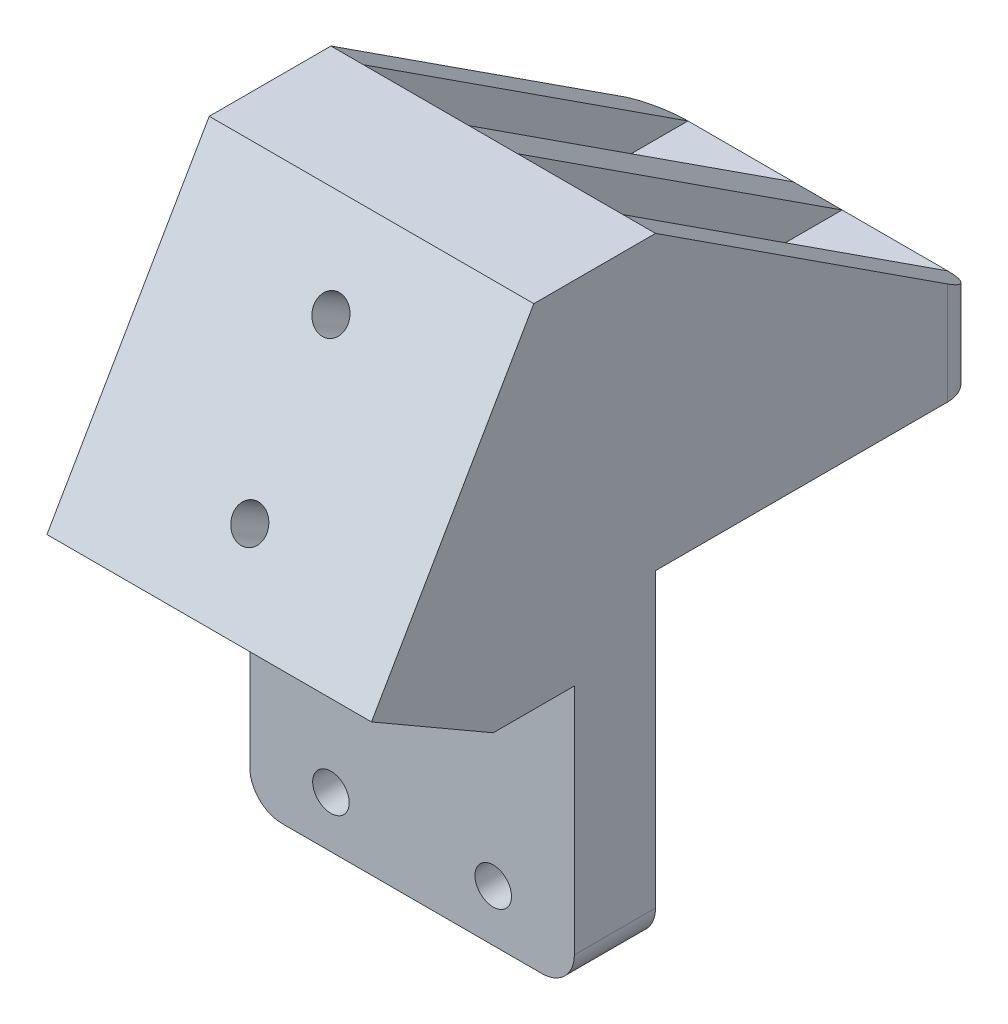
SolidWorks part; units mm, degrees
ref_plane "Plan de face" through (0, 0, 0) normal (0, 0, 1) x (1, 0, 0)
ref_plane "Plan de dessus" through (0, 0, 0) normal (0, 1, 0) x (1, 0, 0)
ref_plane "Plan de droite" through (0, 0, 0) normal (1, 0, 0) x (0, 0, -1)
sketch "Esquisse1" plane through (0, 0, 0) normal (1, 0, 0) x (0, 0, -1)
  line L0 (0, 0) -> (40, 0)
  line L1 (40, 0) -> (40, 10)
  line L2 (40, 10) -> (0, 10)
  line L3 (0, 10) -> (0, 36)
  line L4 (0, 36) -> (-15, 36)
  line L5 (-15, 36) -> (-35, 1.359)
  line L6 (-35, 1.359) -> (-20, -7.3013)
  line L7 (-20, -7.3013) -> (-10, -7.3013)
  line L8 (-10, -7.3013) -> (-10, -40)
  line L9 (-10, -40) -> (0, -40)
  line L10 (0, -40) -> (0, 0)
  point P3 (0, 37.6022)
  point P13 (-19.0235, -4.9783)
  dimension "D1" = 10
  dimension "D2" = 10
  dimension "D3" = 26
  dimension "D4" = 15
  dimension "D5" = 30
  dimension "D6" = 40
  dimension "D7" = 40
  dimension "D8" = 40
  dimension "D9" = 90
  dimension "D10" = 10
extrude "Boss.-Extru.1" add sketch "Esquisse1" along normal blind 40
sketch "Esquisse2" plane through (0, 10, 0) normal (0, 1, 0) x (1, 0, 0)
  line L0 (0, 20) -> (40, 20) construction
  line L1 (0, 40) -> (0, 0) construction
  line L2 (40, 40) -> (40, 0) construction
  line L3 (20, 20) -> (20, 40) construction
  line L4 (40, 40) -> (0, 40) construction
  circle A0 centre (10, 30) radius 2.25
  circle A1 centre (30, 30) radius 2.25
  circle A2 centre (30, 10) radius 2.25
  circle A3 centre (10, 10) radius 2.25
  dimension "D1" = 4.5
  dimension "D2" = 20
  dimension "D3" = 20
extrude "Enlèv. mat.-Extru.1" cut sketch "Esquisse2" against normal through all both and the other way through all
sketch "Esquisse3" plane through (0, 0, 10) normal (0, 0, 1) x (1, 0, 0)
  line L0 (20, -40) -> (20, -23.6506) construction
  line L1 (40, -40) -> (0, -40) construction
  line L2 (20, -23.6506) -> (0, -23.6506) construction
  line L3 (0, -7.3013) -> (0, -40) construction
  circle A0 centre (10, -33.6506) radius 2.25
  circle A1 centre (30, -33.6506) radius 2.25
  circle A2 centre (30, -13.6506) radius 2.25
  circle A3 centre (10, -13.6506) radius 2.25
  dimension "D1" = 20
  dimension "D2" = 20
  dimension "D3" = 4.5
extrude "Enlèv. mat.-Extru.2" cut sketch "Esquisse3" against normal through all both and the other way through all
sketch "Esquisse4" plane through (0, 15.4952, 26.8385) normal (0, 0.5, 0.866) x (1, 0, 0)
  line L0 (20, -16.3231) -> (20, 23.6769) construction
  line L1 (40, -16.3231) -> (0, -16.3231) construction
  line L2 (40, 23.6769) -> (0, 23.6769) construction
  line L3 (20, 3.6769) -> (0, 3.6769) construction
  line L4 (0, 23.6769) -> (0, -16.3231) construction
  circle A0 centre (20, 13.6769) radius 2.1
  circle A1 centre (20, -6.3231) radius 2.1
  dimension "D1" = 4.2
  dimension "D2" = 20
extrude "Enlèv. mat.-Extru.3" cut sketch "Esquisse4" against normal blind 20 and the other way through all
sketch "Esquisse5" plane through (40, 0, 0) normal (1, 0, 0) x (0, 0, -1)
  line L0 (40, 10) -> (0, 36)
  line L1 (0, 36) -> (0, 10)
  line L2 (0, 10) -> (40, 10)
extrude "Boss.-Extru.2" add sketch "Esquisse5" against normal blind 4
extrude "Boss.-Extru.3" add sketch "Esquisse5<2>" along normal blind 4 from surface starting at face at (0, -0.1131, 0.9091)
sketch "Esquisse5<2>" plane through (40, 0, 0) normal (1, 0, 0) x (0, 0, -1) same geometry as "Esquisse5"
extrude "Boss.-Extru.4" add sketch "Esquisse5<3>" along normal blind 3 and the other way blind 3 from offset 20 offset against normal yes
sketch "Esquisse5<3>" plane through (40, 0, 0) normal (1, 0, 0) x (0, 0, -1) same geometry as "Esquisse5"
fillet "Congé1" radius 4 4 edges at (0, 5, -40) (40, 5, -40) (0, -40, 5) (40, -40, 5)
